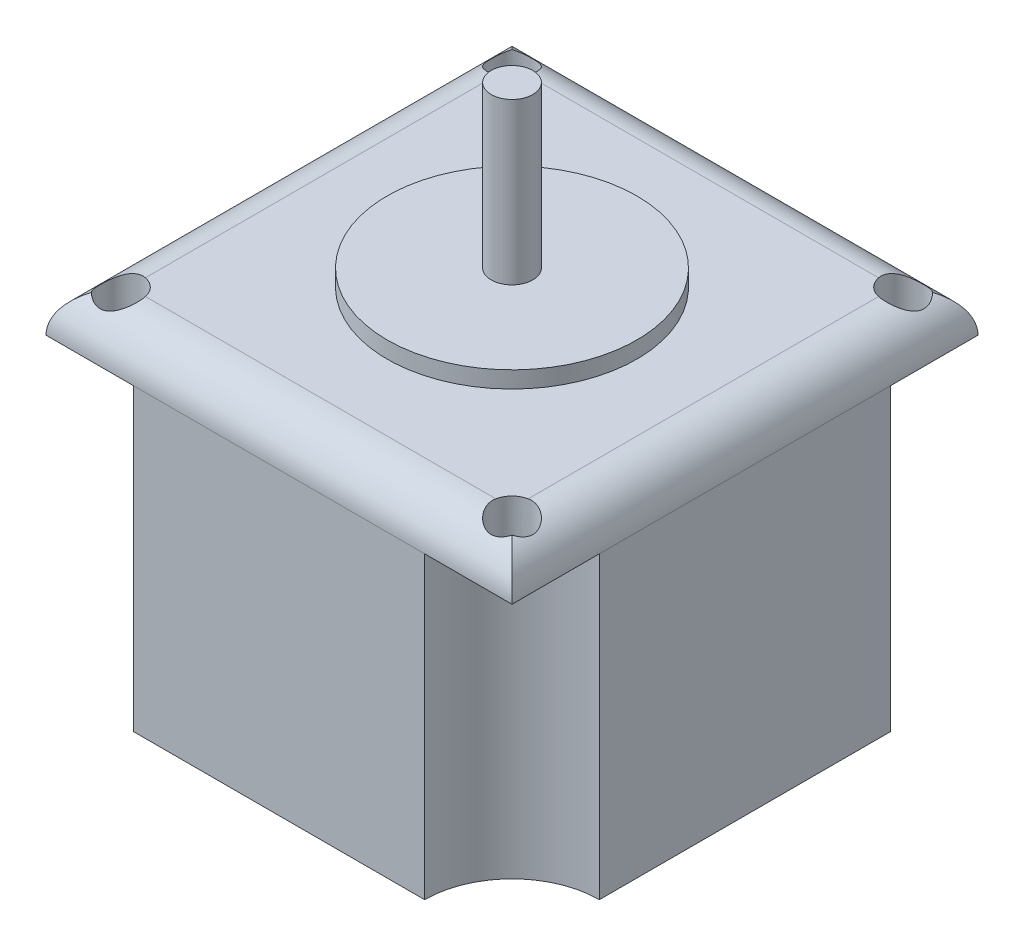
SolidWorks part; units mm, degrees
ref_plane "Piano frontale" through (0, 0, 0) normal (0, 0, 1) x (1, 0, 0)
ref_plane "Piano superiore" through (0, 0, 0) normal (0, 1, 0) x (1, 0, 0)
ref_plane "Piano destro" through (0, 0, 0) normal (1, 0, 0) x (0, 0, -1)
sketch "Schizzo1" plane through (0, 0, 0) normal (0, 1, 0) x (1, 0, 0)
  line L1 (-28, -28) -> (28, -28)
  line L2 (-28, -28) -> (-28, 28)
  line L3 (-28, 28) -> (28, 28)
  line L4 (28, -28) -> (28, 28)
  line L5 (-28, -28) -> (28, 28) construction
  line L6 (-28, 28) -> (28, -28) construction
  point P0 (0, 0)
  dimension "D1" = 56
  dimension "D2" = 56
extrude "Estrusione-Estrusione1" add sketch "Schizzo1" along normal blind 41
sketch "Schizzo2" plane through (0, 41, 0) normal (0, 1, 0) x (1, 0, 0)
  line L1 (-23.5, -23.5) -> (23.5, -23.5)
  line L2 (-23.5, -23.5) -> (-23.5, 23.5)
  line L3 (-23.5, 23.5) -> (23.5, 23.5)
  line L4 (23.5, -23.5) -> (23.5, 23.5)
  line L5 (-23.5, -23.5) -> (23.5, 23.5) construction
  line L6 (-23.5, 23.5) -> (23.5, -23.5) construction
  circle A0 centre (-23.5, 23.5) radius 2.5
  circle A1 centre (23.5, 23.5) radius 2.5
  circle A2 centre (23.5, -23.5) radius 2.5
  circle A3 centre (-23.5, -23.5) radius 2.5
  point P0 (0, 0)
  dimension "D3" = 5
  dimension "D4" = 5
  dimension "D5" = 5
  dimension "D6" = 5
  dimension "D1" = 47
  dimension "D2" = 47
extrude "Taglio-Estrusione1" cut sketch "Schizzo2" against normal blind 41 contours A0 | A1 | A2 | A3
sketch "Schizzo3" plane through (0, 41, 0) normal (0, 1, 0) x (1, 0, 0)
  circle A0 centre (0, 0) radius 15
  dimension "D1" = 30
extrude "Estrusione-Estrusione3" add sketch "Schizzo3" along normal blind 2
sketch "Schizzo4" plane through (0, 43, 0) normal (0, 1, 0) x (1, 0, 0)
  circle A0 centre (0, 0) radius 2.5
  dimension "D1" = 5
extrude "Estrusione-Estrusione4" add sketch "Schizzo4" along normal blind 19.3
sketch "Schizzo5" plane through (0, 0, 0) normal (0, -1, 0) x (1, 0, 0)
  circle A0 centre (-28, 28) radius 10.5
  circle A1 centre (28, 28) radius 10.5
  circle A2 centre (28, -28) radius 10.5
  circle A3 centre (-28, -28) radius 10.5
  dimension "D1" = 21
  dimension "D2" = 21
  dimension "D3" = 21
  dimension "D4" = 21
extrude "Taglio-Estrusione2" cut sketch "Schizzo5" against normal blind 36
fillet "Congé1" radius 5 4 edges at (0, 41, -28) (-28, 41, 0) (0, 41, 28) (28, 41, 0)
